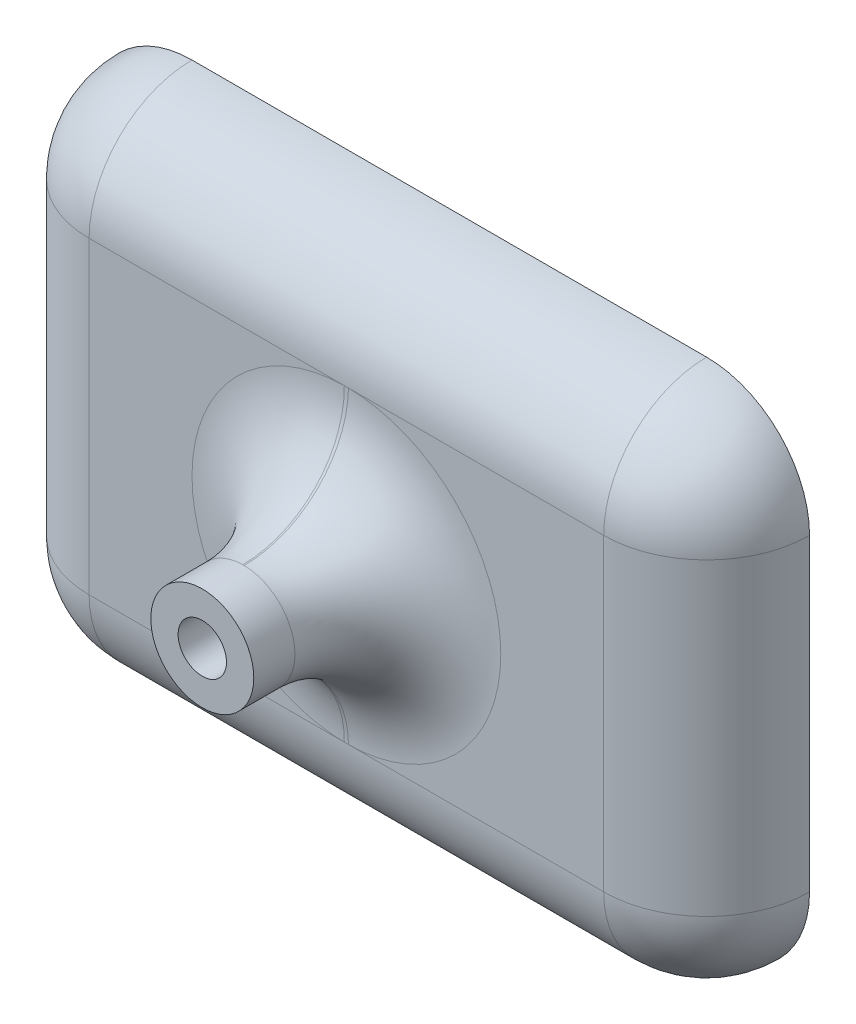
SolidWorks part; units mm, degrees
ref_plane "Plano frontal" through (0, 0, 0) normal (0, 0, 1) x (1, 0, 0)
ref_plane "Plano superior" through (0, 0, 0) normal (0, 1, 0) x (1, 0, 0)
ref_plane "Plano direito" through (0, 0, 0) normal (1, 0, 0) x (0, 0, -1)
sketch "Esboço1" plane through (0, 0, 0) normal (0, 0, 1) x (1, 0, 0)
  line L0 (0, 0) -> (34.1306, 0) construction
  line L1 (34.1306, 0) -> (34.1306, 50) construction
  line L2 (34.1306, 50) -> (-35.8694, 50) construction
  line L3 (-35.8694, 50) -> (-35.8694, 0) construction
  line L4 (-35.8694, 0) -> (0, 0) construction
  line L5 (-35.8694, 50) -> (34.1306, 0) construction
  line L6 (-35.8694, 50) -> (34.1306, 50)
  line L7 (-35.8694, 50) -> (-35.8694, 0)
  line L8 (-35.8694, 0) -> (34.1306, 0)
  line L9 (34.1306, 50) -> (34.1306, 0)
  line L10 (34.1306, 50) -> (-35.8694, 0) construction
  circle A0 centre (-0.8694, 25) radius 2.35
  dimension "D3" = 4.7
  dimension "D1" = 70
  dimension "D2" = 50
extrude "Ressalto-extrusão1" add sketch "Esboço1" along normal blind 10
sketch "Esboço2" plane through (0, 0, 0) normal (0, 0, 1) x (1, 0, 0)
  circle A0 centre (-0.8694, 25) radius 2.35
  circle A1 centre (-0.8694, 25) radius 5.0014
extrude "Ressalto-extrusão2" add sketch "Esboço2" along normal blind 24
fillet "Filete1" radius 10 1 edges at (-0.8694, 0, 10)
fillet "Filete2" radius 10 1 edges at (-0.8694, 50, 10)
fillet "Filete3" radius 10 3 edges at (-35.8694, 47.0711, 7.0711) (-35.8694, 2.9289, 7.0711) (-35.8694, 25, 10)
fillet "Filete4" radius 10 3 edges at (34.1306, 2.9289, 7.0711) (34.1306, 47.0711, 7.0711) (34.1306, 25, 10)
fillet "Filete5" radius 10 1 edges at (4.132, 25, 10)
